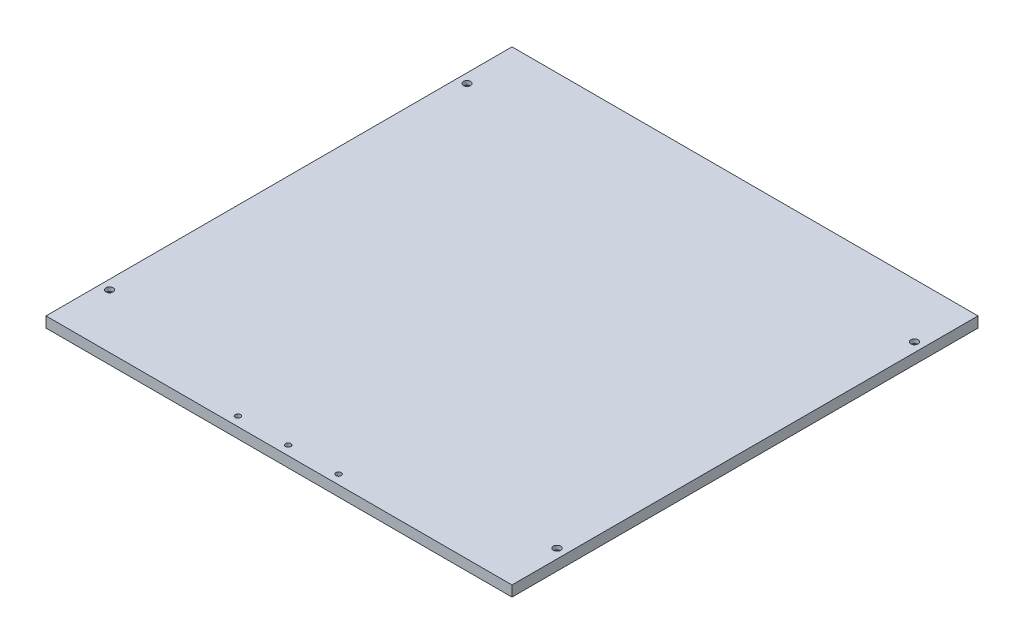
SolidWorks part; units mm, degrees
ref_plane "Front Plane" through (0, 0, 0) normal (0, 0, 1) x (1, 0, 0)
ref_plane "Top Plane" through (0, 0, 0) normal (0, 1, 0) x (1, 0, 0)
ref_plane "Right Plane" through (0, 0, 0) normal (1, 0, 0) x (0, 0, -1)
sketch "PlateSketch2" plane through (0, 0, 0) normal (0, 1, 0) x (1, 0, 0)
  line L1 (0, 0) -> (352, 0)
  line L2 (0, 0) -> (0, 352)
  line L3 (0, 352) -> (352, 352)
  line L4 (352, 0) -> (352, 352)
  circle A0 centre (7, 311) radius 2
  circle A1 centre (345, 311) radius 2
  circle A2 centre (138, 7) radius 2
  circle A3 centre (176, 7) radius 2
  circle A4 centre (214, 7) radius 2
  circle A5 centre (7, 41) radius 2
  circle A6 centre (345, 41) radius 2
  dimension "D5" = 4
  dimension "D10" = 4
  dimension "D1" = 352
  dimension "D2" = 352
  dimension "D3" = 7
  dimension "D4" = 7
  dimension "D6" = 41
  dimension "D7" = 38
  dimension "D8" = 38
  dimension "D9" = 176
  dimension "D11" = 7
  dimension "D12" = 41
extrude "Boss-Extrude1" add sketch "PlateSketch2" along normal blind 8
sketch "BoreSketch1" plane through (0, 8, 0) normal (0, 1, 0) x (1, 0, 0)
  circle A0 centre (7, 311) radius 2.75
  circle A1 centre (345, 311) radius 2.75
  circle A4 centre (7, 311) radius 2 construction
  circle A5 centre (345, 311) radius 2 construction
  circle A6 centre (7, 41) radius 2.75
  circle A7 centre (345, 41) radius 2.75
  dimension "D1" = 5.5
extrude "BoreCut-Extrude1" cut sketch "BoreSketch1" against normal blind 3
equation "\"BuildPlateStandoffHolesDistanceFromLeftOrRightSide\"= 7mm"
equation "\"BuildPlateStandoffHolesDistanceFromFrontOrBackSide\"= 41mm"
equation "\"BedSpringHoleSize\"= \"M4HoleDiameter\""
equation "\"BuildPlateWidth\"= 352mm'Spec"
equation "\"BuildPlateLength\"= 352mm'Spec"
equation "\"D5@PlateSketch2\" = \"BedSpringHoleSize\""
equation "\"D10@PlateSketch2\" = \"BedSpringHoleSize\""
equation "\"BuildPlateBoreDiameter\"= \"M4BoreDiameter\"'Spec"
equation "\"D1@BoreSketch1\" = \"BuildPlateBoreDiameter\""
equation "\"BuildPlateBoreDepth\"= 3mm'Spec"
equation "\"D1@BoreCut-Extrude1\" = \"BuildPlateBoreDepth\""
equation "\"BuildPlateHeight\"= 8mm'Spec"
equation "\"D1@Boss-Extrude1\"=\"BuildPlateHeight\""
equation "\"D1@PlateSketch2\"= \"BuildPlateLength\""
equation "\"D2@PlateSketch2\"=\"BuildPlateWidth\""
equation "\"D9@PlateSketch2\"=\"BuildPlateWidth\"/2"
equation "\"BuildPlateFlankingHoles\"= 38mm"
equation "\"D7@PlateSketch2\"=\"BuildPlateFlankingHoles\""
equation "\"D6@PlateSketch2\"=\"BuildPlateStandoffHolesDistanceFromFrontOrBackSide\""
equation "\"D3@PlateSketch2\"=\"BuildPlateStandoffHolesDistanceFromLeftOrRightSide\""
equation "\"D4@PlateSketch2\"=\"BuildPlateStandoffHolesDistanceFromLeftOrRightSide\""
equation "\"BuildPlateStandoffHolesDistanceFromFront\"= 7mm"
equation "\"D11@PlateSketch2\"=\"BuildPlateStandoffHolesDistanceFromFront\""
equation "\"D12@PlateSketch2\"=\"BuildPlateStandoffHolesDistanceFromFrontOrBackSide\""
equation "\"M4HoleDiameter\"= 4mm"
equation "\"M4BoreDiameter\"= 5.5mm"
